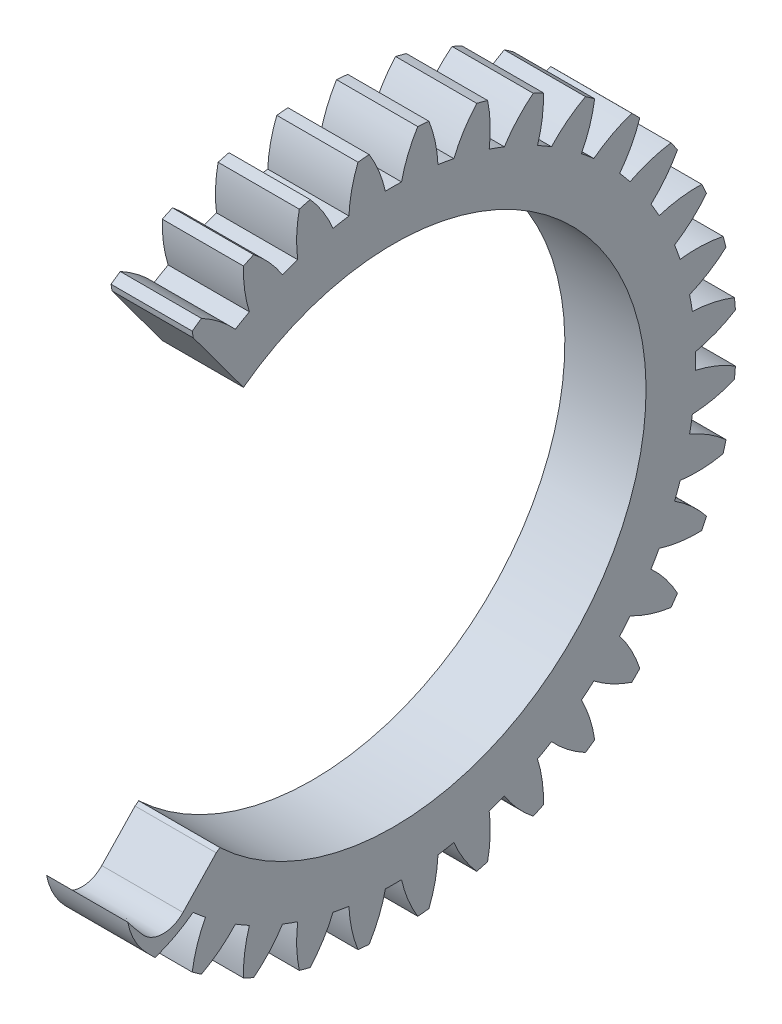
SolidWorks part; units mm, degrees
ref_plane "Plane1" through (0, 0, 0) normal (0, 0, 1) x (1, 0, 0)
ref_plane "Plane2" through (0, 0, 0) normal (0, 1, 0) x (1, 0, 0)
ref_plane "Plane3" through (0, 0, 0) normal (1, 0, 0) x (0, 0, -1)
sketch "HoldingSke" plane through (0, 0, 0) normal (0, 1, 0) x (1, 0, 0)
  line L0 (0, 0) -> (0.4045, -0.2939)
  line L1 (-15, 0) -> (100, 0) construction
  line L2 (0, 0) -> (-2.1039, 2.3779)
  line L3 (0, 0) -> (-11.863, 4.5341)
  line L4 (0, 0) -> (6.9867, 5.0761)
  line L5 (0, 0) -> (-46.8476, -17.4728)
  line L6 (0, 0) -> (-7.4607, -5.0337)
  line L7 (-2.1039, 2.3779) -> (8.6586, 51.2059)
  line L8 (-76.2, 54.61) -> (-71.9, 54.61)
  line L9 (-71.009, 38.7566) -> (-53.1078, 45.2721)
  line L10 (-76.2, 71.12) -> (104.1128, 71.12)
  line L11 (0, 0) -> (-9, 0)
  line L12 (-76.2, 101.6) -> (-76.133, 101.6)
  line L13 (24.9733, 27.94) -> (52.9518, 28.4284)
  line L14 (24.9733, 27.94) -> (24.9743, 27.94)
  line L15 (24.9733, 27.94) -> (100.4006, 29.5858)
  line L16 (-63.627, -2) -> (-12.827, -2)
  circle A0 centre (0, 0) radius 28
  circle A1 centre (0, 0) radius 33.499
  circle A2 centre (0, 0) radius 37.5
  circle A3 centre (0, 0) radius 28
  dimension "Num_teeth" = 36
  dimension "Pitch_radius" = 180.3128
  dimension "Width" = 9
  dimension "Thickness" = 9
sketch "BasProSke" plane through (0, 0, 0) normal (0, 1, 0) x (1, 0, 0)
  line L0 (-10, 0) -> (60, 0) construction
  line L1 (0, 0) -> (0, 38)
  line L2 (0, 0) -> (9, 0)
  line L3 (9, 0) -> (9, 38)
  line L4 (9, 38) -> (0, 38)
  dimension "Thickness" = 9
  dimension "Diameter" = 76
revolve "Base-Revolve" add sketch "BasProSke" angle 360 about L0
sketch "TooCutSke" plane through (0, 0, 0) normal (1, 0, 0) x (0, 0, -1)
  line L1 (0, 0) -> (0, 107) construction
  line L2 (0, 0) -> (-1.6875, 35.9604) construction
  line L3 (0, 0) -> (-6.2701, 71.6676) construction
  line L4 (-1.6875, 35.9604) -> (-3.135, 35.8338) construction
  arc A0 (0.8949, 33.487) -> (-0.8949, 33.487) centre (0, 0) ccw
  arc A1 (2.7061, 37.929) -> (-2.7061, 37.929) centre (0, 0) ccw
  circle A2 centre (0, 0) radius 36 construction
  circle A3 centre (0, 0) radius 33.8289 construction
  arc A4 (-0.8949, 33.487) -> (-2.7061, 37.929) centre (-14.9484, 30.347) ccw
  arc A5 (2.7061, 37.929) -> (0.8949, 33.487) centre (14.9484, 30.347) ccw
extrude "ToothCut" cut sketch "TooCutSke" along normal through all
fillet "Breaks" [suppressed] radius 0.04 tangent propagation no
fillet "RootFillets" [suppressed] radius 0.501
pattern_circular "TeethCuts" count 36 every 10 about axis through (-10, 0, 0) along (1, 0, 0) of "ToothCut", "RootFillets", "Breaks"
sketch "HubNeaOneSke" plane through (0, 0, 0) normal (-1, 0, 0) x (0, 0, 1)
  circle A0 centre (0, 0) radius 33.499
  dimension "Diameter" = 66.998
extrude "HubNearOne" [suppressed] add sketch "HubNeaOneSke" along normal blind 41.0001
sketch "HubNeaBotSke" plane through (0, 0, 0) normal (-1, 0, 0) x (0, 0, 1)
  circle A0 centre (0, 0) radius 33.499
  dimension "Diameter" = 66.998
extrude "HubNearBoth" [suppressed] add sketch "HubNeaBotSke" along normal blind 20.5
ref_plane "FarPln" through (9, 0, 0) normal (1, 0, 0) x (0, 0, -1)
sketch "HubFarSke" plane through (9, 0, 0) normal (1, 0, 0) x (0, 0, -1)
  circle A0 centre (0, 0) radius 33.499
  dimension "Diameter" = 66.998
extrude "HubFar" [suppressed] add sketch "HubFarSke" along normal blind 20.5
sketch "BorSke" plane through (0, 0, 0) normal (1, 0, 0) x (0, 0, -1)
  circle A0 centre (0, 0) radius 28
  dimension "Diameter" = 56
extrude "Bore" cut sketch "BorSke" along normal mid plane 100.0001
sketch "KeySke" plane through (0, 0, 0) normal (1, 0, 0) x (0, 0, -1)
  line L0 (-8, 0) -> (-8, 32.3)
  line L1 (-8, 32.3) -> (8, 32.3)
  line L2 (8, 32.3) -> (8, 0)
  line L3 (0, 0) -> (0, 34) construction
  line L4 (-8, 0) -> (8, 0)
  dimension "Width" = 16
extrude "Keyway" [suppressed] cut sketch "KeySke" along normal mid plane 100.0001
pattern_circular "Keyway2" [suppressed] count 2 every 90 about axis through (-10, 0, 0) along (1, 0, 0) reverse direction yes
sketch "Szkic1" plane through (0, 0, 0) normal (1, 0, 0) x (0, 0, -1)
  line L0 (0, 0) -> (-27.328, 37.0259)
  line L1 (-27.328, 37.0259) -> (-47.6164, -10.233)
  line L2 (-47.6164, -10.233) -> (0, 0)
extrude "Wytnij-wyciągnięcie1" cut sketch "Szkic1" along normal through all
sketch "Szkic2" plane through (0, 0, 0) normal (1, 0, 0) x (0, 0, -1)
  line L0 (-19.6433, -20.6493) -> (-23.3286, -24.5233) construction
  line L1 (-19.6433, -20.6493) -> (-23.3286, -24.5233)
  line L2 (-24.5118, 27.7159) -> (-14.2182, -16.6493)
  line L3 (-14.2182, -16.6493) -> (-19.6433, -20.6493)
  line L4 (-24.5118, 27.7159) -> (-50.9594, 25.255)
  line L5 (-50.9594, 25.255) -> (-37.7356, -29.3697)
  line L6 (-37.7356, -29.3697) -> (-27.7664, -24.4546)
  line L7 (-26.426, -27.3069) -> (-27.3069, -26.426)
  line L8 (-26.426, -27.3069) -> (-25.0675, -25.4318)
  arc A0 (-24.5118, 27.7159) -> (-27.7664, -24.4546) centre (0, 0) ccw construction
  arc A1 (-24.5118, 27.7159) -> (-27.7664, -24.4546) centre (0, 0) ccw
  arc A2 (-27.3069, -26.426) -> (-29.4473, -22.4022) centre (-21.7924, -20.9115) cw
  spline S0 degree 3 poles (291312.4, 361097.5289) (7936.846, 10340.8304) (-157.3275, 71.8425) (-27.1426, -24.9996) (-26.9606, -25.1074) (-26.5829, -25.2806) (-26.3868, -25.3469) (-25.9801, -25.4387) (-25.7711, -25.4633) (-25.3572, -25.469) (-25.1483, -25.4503) (-24.7384, -25.37) (-24.5404, -25.3094) (-24.158, -25.1482) (-23.9725, -25.0463) (119.762, 74.3749) (-8789.4767, 12005.1554) (-281667.9505, 368928.1083) knots -97.673273 -97.673273 -97.673273 -97.673273 0.125 0.125 0.25 0.25 0.375 0.375 0.5 0.5 0.625 0.625 0.75 0.75 0.875 0.875 106.009477 106.009477 106.009477 106.009477 only from (-27.7664, -24.4546) to (-23.3286, -24.5233) construction
  spline S1 degree 3 poles (-27.7664, -24.4546) (-27.6277, -24.6121) (-27.4749, -24.7523) (-27.1426, -24.9996) (-26.9606, -25.1074) (-26.5829, -25.2806) (-26.3868, -25.3469) (-25.9801, -25.4387) (-25.7711, -25.4633) (-25.3572, -25.469) (-25.1483, -25.4503) (-24.7384, -25.37) (-24.5404, -25.3094) (-24.158, -25.1482) (-23.9725, -25.0463) (-23.6312, -24.8102) (-23.4733, -24.6754) (-23.3286, -24.5233) knots 0 0 0 0 0.125 0.125 0.25 0.25 0.375 0.375 0.5 0.5 0.625 0.625 0.75 0.75 0.875 0.875 1 1 1 1
extrude "Wytnij-wyciągnięcie2" cut sketch "Szkic2" against normal blind 43 and the other way through all contours A1 L4 L5 L6 | A1 S1 L1 L3 L2 region at (0, -1.5762, 26.5296) region at (0, 4.8425, 39.1923)
extrude "Dodanie-wyciągnięcie1" add sketch "Szkic2<3>" along normal up to surface (9 mm away) contours A2 L6 A1 | S1 L6 A2 L7 L8 region at (0, -25.7946, 26.8655) region at (0, -23.8723, 28.649) up to face at (9, -1.2954, -9.9994)
sketch "Szkic2<3>" plane through (0, 0, 0) normal (1, 0, 0) x (0, 0, -1) same geometry as "Szkic2"
equation "' \"Module@HoldingSke\" = 6.35"
equation "' \"Num_teeth@HoldingSke\" = 12"
equation "' \"Ap@HoldingSke\" =  20"
equation "' \"Ap@HoldingSke\" = 20"
equation "' \"Width@HoldingSke\" = 0.5 * 25.4"
equation "' \"Hub_dia@HoldingSke\"= 1 * 25.4"
equation "' \"Hub_dia@HoldingSke\" = 1 * 25.4"
equation "' \"Overall_len@HoldingSke\" = 1.0 * 25.4"
equation "' \"Bore@HoldingSke\" = 0.75 * 25.4"
equation "' \"T_dim@HoldingSke\" = 0.1 * 25.4"
equation "' \"Width@KeySke\" = 0.25 * 25.4"
equation "' \"Show_teeth@HoldingSke\" = 13"
equation "' \"Backlash@HoldingSke\" = 0.009 * 25.4"
equation "' \"Addendum_fac@HoldingSke\" = 1.0"
equation "' \"Dedendum_fac@HoldingSke\" = 1.25"
equation "' \"Dedendum_add@HoldingSke\" = 0.00005 * 25.4"
equation "' \"Clearance_fac@HoldingSke\" = 0.25"
equation "\"Pitch@HoldingSke\" = 1 / \"Module@HoldingSke\""
equation "\"Overcut_dia@TooCutSke\" = (\"Num_teeth@HoldingSke\" + 2 * \"Addendum_fac@HoldingSke\") / \"Pitch@HoldingSke\" + 0.002 * 25.4"
equation "\"Pitch_dia@TooCutSke\" = \"Num_teeth@HoldingSke\" / \"Pitch@HoldingSke\""
equation "\"Base_dia@TooCutSke\" = \"Num_teeth@HoldingSke\" / \"Pitch@HoldingSke\" * cos((\"Ap@HoldingSke\"  * 3.14159265 / 180))"
equation "\"Root_dia@TooCutSke\" = (\"Num_teeth@HoldingSke\" + 2) / \"Pitch@HoldingSke\" - 2 * (\"Addendum_fac@HoldingSke\" + \"Dedendum_fac@HoldingSke\") / \"Pitch@HoldingSke\" - \"Dedendum_add@HoldingSke\" * 2"
equation "\"Half_ang@TooCutSke\" = 180 / \"Num_teeth@HoldingSke\""
equation "\"Half_CT@TooCutSke\" = \"Num_teeth@HoldingSke\" / \"Pitch@HoldingSke\" * sin((3.14159265 / 2 / \"Num_teeth@HoldingSke\")) / 2 - 7 * \"Backlash@HoldingSke\" / 4"
equation "\"Flank_rad@TooCutSke\" = \"Num_teeth@HoldingSke\" / \"Pitch@HoldingSke\" / 5"
equation "\"Radius@RootFillets\" = \"Clearance_fac@HoldingSke\" / \"Pitch@HoldingSke\" + \"Dedendum_add@HoldingSke\""
equation "\"Break_rad@Breaks\" = 0.02 / \"Pitch@HoldingSke\""
equation "\"Thickness@HoldingSke\" = \"Width@HoldingSke\""
equation "\"OAL@HoldingSke\" = \"Thickness@HoldingSke\""
equation "\"MHD@HoldingSke\" = (\"Num_teeth@HoldingSke\" + 2) / \"Pitch@HoldingSke\" - 2 * (\"Addendum_fac@HoldingSke\" + \"Dedendum_fac@HoldingSke\")  / \"Pitch@HoldingSke\" - \"Dedendum_add@HoldingSke\" * 2"
equation "\"MBD@HoldingSke\" = (\"Num_teeth@HoldingSke\" + 2) / \"Pitch@HoldingSke\" - 2 * (\"Addendum_fac@HoldingSke\" + \"Dedendum_fac@HoldingSke\")  / \"Pitch@HoldingSke\" - \"Dedendum_add@HoldingSke\" * 2 - 0.002 * 25.4"
equation "\"MHD@HoldingSke\" = ((sgn( \"MHD@HoldingSke\" - \"Hub_dia@HoldingSke\" )-1)*( \"MHD@HoldingSke\" - \"Hub_dia@HoldingSke\" ))/-2+ \"Hub_dia@HoldingSke\""
equation "\"MBD@HoldingSke\" = ((sgn( \"MBD@HoldingSke\" - \"Bore@HoldingSke\" )-1)*( \"MBD@HoldingSke\" - \"Bore@HoldingSke\" ))/-2+ \"Bore@HoldingSke\""
equation "\"OAL@HoldingSke\" = ((sgn( \"OAL@HoldingSke\" - \"Overall_len@HoldingSke\" )+1)*( \"OAL@HoldingSke\" - \"Overall_len@HoldingSke\" ))/2 + \"Overall_len@HoldingSke\" + 0.000002 * 25.4"
equation "\"Num_teeth@TeethCuts\" = int( \"Show_teeth@HoldingSke\" ) + 1"
equation "\"Num_teeth@TeethCuts\" = ((sgn( \"Num_teeth@TeethCuts\" - \"Num_teeth@HoldingSke\" )-1)*( \"Num_teeth@TeethCuts\" - \"Num_teeth@HoldingSke\" ))/-2+ \"Num_teeth@HoldingSke\""
equation "\"Num_teeth@TeethCuts\" = ((sgn( \"Num_teeth@TeethCuts\" - 2.0)+1)*( \"Num_teeth@TeethCuts\" - 2.0))/2 +2.0"
equation "\"Angle@TeethCuts\" = 360.0 / \"Num_teeth@HoldingSke\""
equation "\"Diameter@BasProSke\" = (\"Num_teeth@HoldingSke\" + 2 * \"Addendum_fac@HoldingSke\") / \"Pitch@HoldingSke\""
equation "\"Thickness@BasProSke\"  = \"Thickness@HoldingSke\""
equation "' \"Fillet_rad@BasProSke\" =  \"Thickness@HoldingSke\" * 0.05"
equation "' \"Fillet_rad@BasProSke\" = \"Thickness@HoldingSke\" * 0.05"
equation "\"MHD@HoldingSke\" = ((sgn( \"MHD@HoldingSke\" - \"Root_dia@TooCutSke\" )-1)*( \"MHD@HoldingSke\" - \"Root_dia@TooCutSke\" ))/-2+ \"Root_dia@TooCutSke\""
equation "\"Diameter@HubNeaOneSke\" = \"MHD@HoldingSke\""
equation "\"Length@HubNearOne\" = \"OAL@HoldingSke\" - \"Thickness@BasProSke\""
equation "\"Diameter@HubNeaBotSke\" = \"MHD@HoldingSke\""
equation "\"Length@HubNearBoth\" = ( \"OAL@HoldingSke\" - \"Thickness@BasProSke\" ) / 2.0"
equation "\"Thickness@FarPln\" = \"Thickness@BasProSke\""
equation "\"Diameter@HubFarSke\" = \"MHD@HoldingSke\""
equation "\"Length@HubFar\" = ( \"OAL@HoldingSke\" - \"Thickness@BasProSke\" ) / 2.0"
equation "\"Diameter@BorSke\" = \"MBD@HoldingSke\""
equation "\"D1@Bore\" = \"OAL@HoldingSke\" * 2.0"
equation "\"D1@Keyway\" = \"OAL@HoldingSke\" * 2.0"
equation "\"Offset@KeySke\" = \"T_dim@HoldingSke\" + \"MBD@HoldingSke\" / 2.0"
